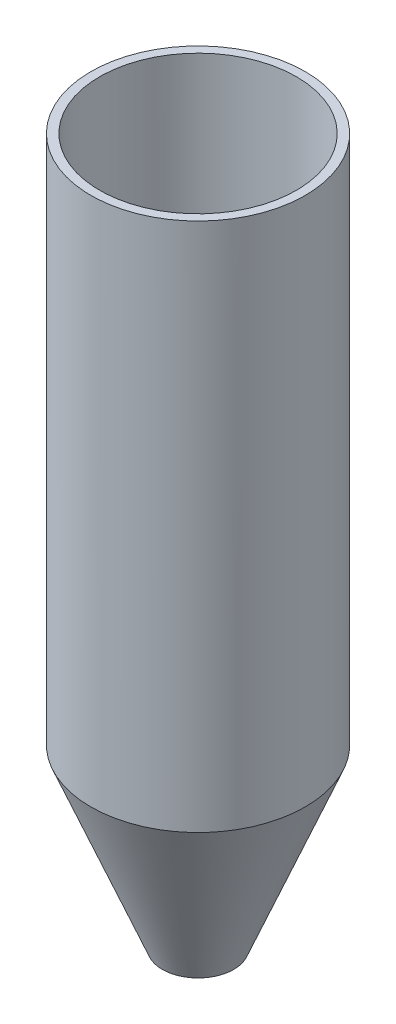
SolidWorks part; units mm, degrees
material "Alumina"
ref_plane "Front Plane" through (0, 0, 0) normal (0, 0, 1) x (1, 0, 0)
ref_plane "Top Plane" through (0, 0, 0) normal (0, 1, 0) x (1, 0, 0)
ref_plane "Right Plane" through (0, 0, 0) normal (1, 0, 0) x (0, 0, -1)
ref_axis "X-axis" through (-88.99, 0, 0) along (1, 0, 0)
ref_axis "Y-axis" through (0, 55, 0) along (0, -1, 0)
ref_axis "Z-axis" through (0, 0, -88.99) along (0, 0, 1)
sketch "Sketch1" plane through (0, 0, 0) normal (0, 0, 1) x (1, 0, 0)
  line L0 (0, 0) -> (0, 2.3582) construction
  line L1 (-1.215, 9) -> (-1.215, 3)
  line L2 (-1.215, 3) -> (0, 0)
  line L3 (-1.115, 9) -> (-1.115, 3.0195)
  line L4 (-1.115, 3.0195) -> (0, 0.2664)
  line L6 (-1.215, 9) -> (-1.115, 9)
  line L7 (0, 0) -> (0, 0.2664)
  line L8 (-1.115, 3.0195) -> (0.0927, 0.0375) construction
  dimension "D1" = 2.43
  dimension "D2" = 9
  dimension "D3" = 6
  dimension "D4" = 0.1
revolve "Revolve1" add sketch "Sketch1" angle 360 about L0
sketch "Sketch2" plane through (0, 0, 0) normal (0, 1, 0) x (1, 0, 0)
  circle A0 centre (0, 0) radius 0.405
  dimension "D1" = 0.81
extrude "Cut-Extrude1" cut sketch "Sketch2" along normal blind 10
